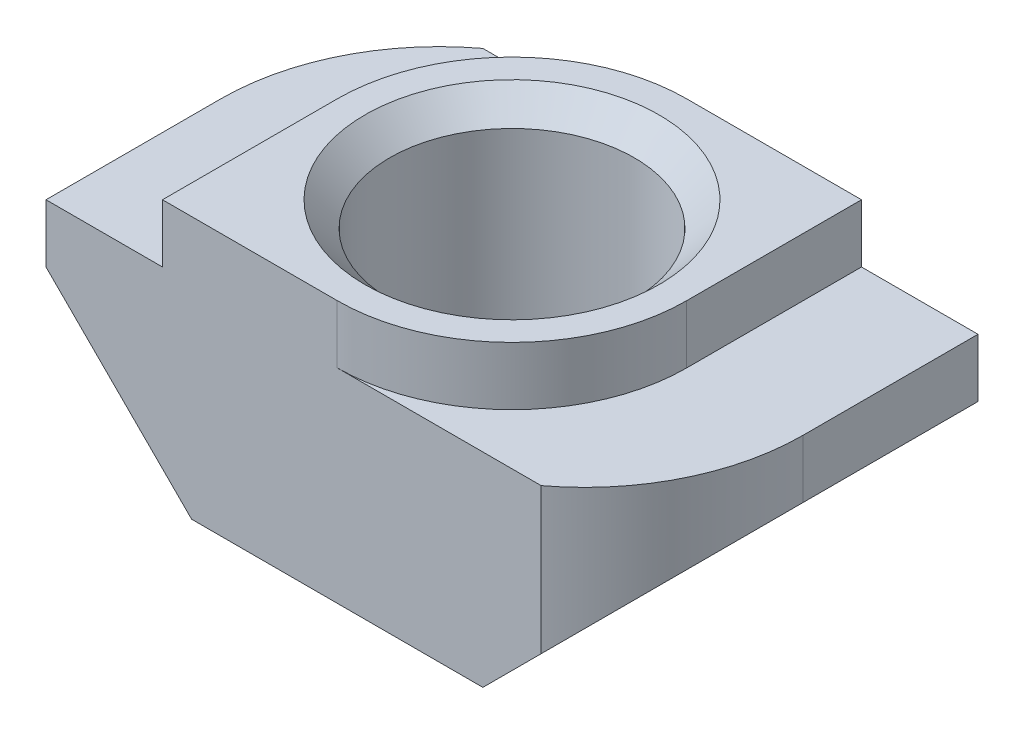
SolidWorks part; units mm, degrees
ref_plane "Front" through (0, 0, 0) normal (0, 0, 1) x (1, 0, 0)
ref_plane "Top" through (0, 0, 0) normal (0, 1, 0) x (1, 0, 0)
ref_plane "Right" through (0, 0, 0) normal (1, 0, 0) x (0, 0, -1)
sketch "Sketch1" plane through (0, 0, 0) normal (0, 0, 1) x (1, 0, 0)
  line L0 (0, 0) -> (0, 4.5) construction
  line L1 (-3, 4.5) -> (3, 4.5)
  line L2 (3, 4.5) -> (3, 3.5)
  line L3 (3, 3.5) -> (5, 3.5)
  line L4 (5, 3.5) -> (5, 2.5)
  line L5 (5, 2.5) -> (2.5, 0)
  line L6 (2.5, 0) -> (-2.5, 0)
  line L7 (-5, 2.5) -> (-2.5, 0)
  line L8 (-5, 3.5) -> (-5, 2.5)
  line L9 (-3, 3.5) -> (-5, 3.5)
  line L10 (-3, 4.5) -> (-3, 3.5)
  dimension "D1" = 135
  dimension "D2" = 10
  dimension "D3" = 4.5
  dimension "D4" = 6
  dimension "D5" = 1
  dimension "D6" = 1
extrude "Boss-Extrude1" add sketch "Sketch1" along normal blind 6
sketch "Sketch2" plane through (0, 4.5, 0) normal (0, 1, 0) x (1, 0, 0)
  line L2 (0, 0) -> (0, -3) construction
  line L3 (0, -3) -> (-3, -3) construction
  line L4 (-3, -6) -> (-3, 0) construction
  line L5 (3, -6) -> (3, 0) construction
  line L6 (0, -6) -> (3, -6)
  line L7 (5, -6) -> (3, -6) construction
  line L8 (3, -6) -> (3, -3)
  line L9 (0, 0) -> (-3, 0)
  line L10 (-3, 0) -> (-3, -3)
  circle A0 centre (0, -3) radius 3 construction
  arc A1 (3, -3) -> (0, -6) centre (0, -3) cw
  arc A2 (-3, -3) -> (0, 0) centre (0, -3) cw
extrude "Cut-Extrude1" cut sketch "Sketch2" against normal up to surface (1 mm away) up to face at (-4, 3.5, 3)
sketch "Sketch3" plane through (0, 3.5, 0) normal (0, 1, 0) x (1, 0, 0)
  line L0 (5, -6) -> (5, 0) construction
  line L1 (5, -6) -> (0, -6) construction
  line L2 (5, -3) -> (5, -6)
  line L3 (5, -6) -> (3.5, -6)
  line L4 (0, 0) -> (0, -3) construction
  line L5 (0, -3) -> (3, -3) construction
  line L6 (-5, 0) -> (-3.5, 0)
  line L7 (-5, -3) -> (-5, 0)
  arc A0 (5, -3) -> (3.5, -6) centre (1.25, -3) cw
  arc A1 (-5, -3) -> (-3.5, 0) centre (-1.25, -3) cw
  point P21 (0, -3)
  dimension "D1" = 1.5
  dimension "D2" = 2
extrude "Cut-Extrude2" cut sketch "Sketch3" against normal through all
hole_wizard "M5x0.8 Tapped Hole1" positions "Sketch4" profile "Sketch5" tap size "M5x0.8" standard "ANSI Metric" end condition through all
sketch "Sketch4" plane through (0, 4.5, 0) normal (0, 1, 0) x (1, 0, 0)
  line L0 (0, 0) -> (0, -3) construction
  line L1 (0, -3) -> (3, -3) construction
  point P0 (0, -3)
sketch "Sketch5" plane through (0, 4.5, 3) normal (1, 0, 0) x (0, 0, 1)
  line L0 (0, 0) -> (0, 4.5)
  line L1 (0, 4.5) -> (2.1, 4.5)
  line L2 (2.1, 4.5) -> (2.1, 0.425)
  line L3 (2.1, 0.425) -> (2.525, 0)
  line L5 (2.525, 0) -> (0, 0)
  line L6 (-2.1, 0.425) -> (-2.525, 0) construction
  line L11 (0, -6.35) -> (0, 107.95) construction
  dimension "Thru Tap Drill Dia." = 4.2
  dimension "Thru Tap Drill Depth" = 4.5
  dimension "Near C'Sink Dia." = 5.05
  dimension "Near C'Sink Angle" = 90
cosmetic thread "Hole Thread1" parameters "D2"=5
